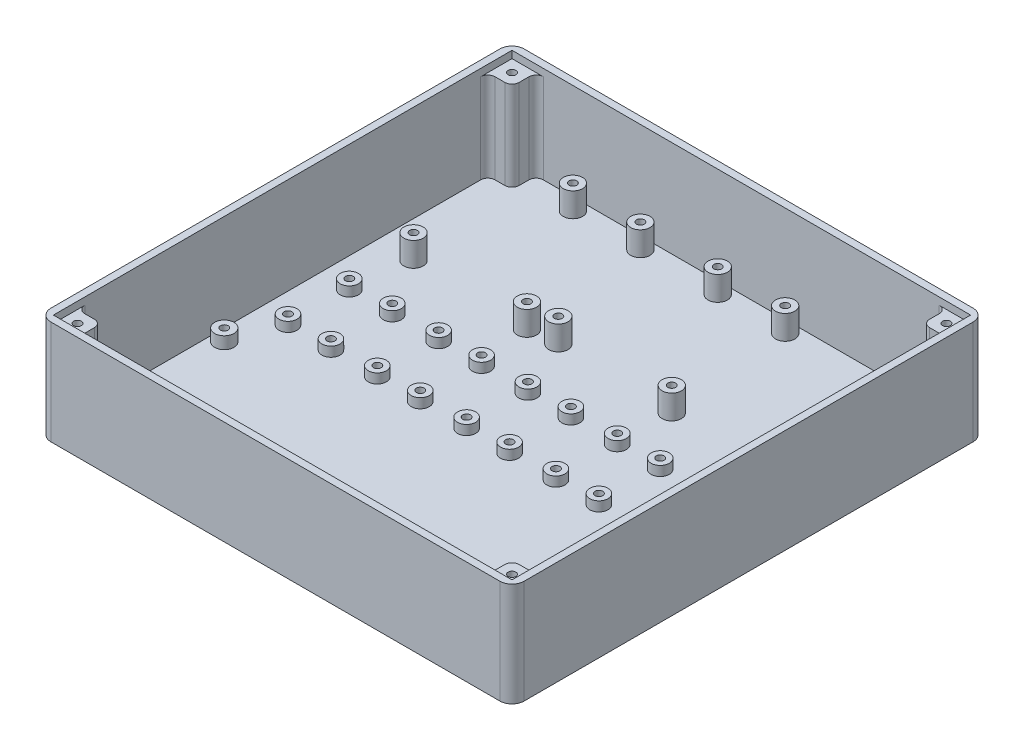
SolidWorks part; units mm, degrees
ref_plane "Front Plane" through (0, 0, 0) normal (0, 0, 1) x (1, 0, 0)
ref_plane "Top Plane" through (0, 0, 0) normal (0, 1, 0) x (1, 0, 0)
ref_plane "Right Plane" through (0, 0, 0) normal (1, 0, 0) x (0, 0, -1)
sketch "Sketch1" plane through (0, 0, 0) normal (0, 1, 0) x (1, 0, 0)
  line L1 (-95, -95) -> (95, -95)
  line L2 (-95, -95) -> (-95, 95)
  line L3 (-95, 95) -> (95, 95)
  line L4 (95, -95) -> (95, 95)
  point P4 (0, -95)
  point P5 (-95, 0)
  dimension "D1" = 190
  dimension "D2" = 190
extrude "Boss-Extrude1" add sketch "Sketch1" along normal blind 40 contours L1 L4 L3 L2
shell "Shell1" thickness 3 removed face at (0, 40, 0) outward yes
fillet "Fillet1" radius 5 4 edges at (-98, 18.5, -98) (98, 18.5, -98) (98, 18.5, 98) (-98, 18.5, 98)
sketch "Sketch5" plane through (0, 0, 0) normal (0, 1, 0) x (1, 0, 0)
  line L3 (-95, 95) -> (-85, 95)
  line L4 (-95, 95) -> (-95, 85)
  line L5 (-95, 85) -> (-85, 85)
  line L6 (-85, 95) -> (-85, 85)
  line L7 (-95, -95) -> (-95, 95) construction
  circle A0 centre (-90, 90) radius 1.6
  dimension "D1" = 3.2
  dimension "D2" = 10
  dimension "D3" = 5
  dimension "D4" = 10
  dimension "D5" = 5
extrude "Boss-Extrude3" add sketch "Sketch5" along normal blind 37
mirror "Mirror1" about plane through (0, 0, 0) normal (1, 0, 0) of "Boss-Extrude3"
mirror "Mirror2" about plane through (0, 0, 0) normal (0, 0, 1) of "Mirror1"
fillet "Fillet3" radius 3 12 edges at (95, 18.5, 85) (85, 18.5, 85) (85, 18.5, 95) (95, 18.5, -85) (85, 18.5, -85) (85, 18.5, -95) (-85, 18.5, -95) (-85, 18.5, -85) (-95, 18.5, -85) (-85, 18.5, 85) (-95, 18.5, 85) (-85, 18.5, 95)
sketch "Sketch6" plane through (0, -3, 0) normal (0, 1, 0) x (1, 0, 0)
  line L0 (-65, 15.4) -> (-65, -10) construction
  circle A0 centre (-65, 15.4) radius 3.75
  circle A1 centre (-65, 15.4) radius 1.6
  circle A2 centre (-65, -10) radius 1.6
  circle A3 centre (-65, -10) radius 3.75
  circle A4 centre (-82.8, 15.4) radius 3.75
  circle A5 centre (-82.8, -10) radius 3.75
  circle A6 centre (-82.8, 15.4) radius 1.6
  circle A7 centre (-82.8, -10) radius 1.6
  dimension "D1" = 3.2
  dimension "D2" = 7.5
  dimension "D3" = 25.4
  dimension "D4" = 65
  dimension "D5" = 2
  dimension "D6" = 17.8
  dimension "D7" = 10
extrude "Boss-Extrude4" add sketch "Sketch6" along normal blind 7
pattern_linear "LPattern1" count 5 spacing 37 along (1, 0, 0) of "Boss-Extrude4"
sketch "Sketch7" plane through (0, 0, 0) normal (0, 1, 0) x (1, 0, 0)
  line L0 (-95, -82) -> (-95, 82) construction
  line L1 (-82, -95) -> (82, -95) construction
  circle A0 centre (-90, -29.2) radius 4
  circle A1 centre (-90, -29.2) radius 1.6
  circle A2 centre (-90, -80) radius 4
  circle A3 centre (-90, -80) radius 1.6
  circle A4 centre (70, -80) radius 4
  circle A5 centre (70, -80) radius 1.6
  circle A6 centre (70, -29.2) radius 4
  circle A7 centre (70, -29.2) radius 1.6
  dimension "D1" = 3.2
  dimension "D2" = 8
  dimension "D3" = 160
  dimension "D4" = 50.8
  dimension "D5" = 5
  dimension "D6" = 15
extrude "Boss-Extrude5" add sketch "Sketch7" along normal blind 5
sketch "Sketch8" plane through (0, 0, 0) normal (0, 1, 0) x (1, 0, 0)
  line L0 (-36.82, 90) -> (-31.74, 37.93) construction
  line L1 (-31.74, 37.93) -> (-80, 39.2) construction
  line L2 (-95, -82) -> (-95, 82) construction
  line L5 (-82, 95) -> (82, 95) construction
  circle A0 centre (-31.74, 37.93) radius 4
  circle A1 centre (-31.74, 37.93) radius 1.6
  circle A2 centre (-36.82, 90) radius 4
  circle A3 centre (-36.82, 90) radius 1.6
  circle A4 centre (-80, 39.2) radius 4
  circle A5 centre (-80, 39.2) radius 1.6
  circle A6 centre (-64.76, 90) radius 4
  circle A7 centre (-64.76, 90) radius 1.6
  dimension "D8" = 3.2
  dimension "D9" = 8
  dimension "D1" = 1.27
  dimension "D2" = 48.26
  dimension "D3" = 50.8
  dimension "D4" = 15.24
  dimension "D5" = 27.94
  dimension "D6" = 15
  dimension "D7" = 5
extrude "Boss-Extrude6" add sketch "Sketch8" along normal blind 10
pattern_linear "LPattern2" count 2 spacing 60 along (1, 0, 0) of "Boss-Extrude6"
